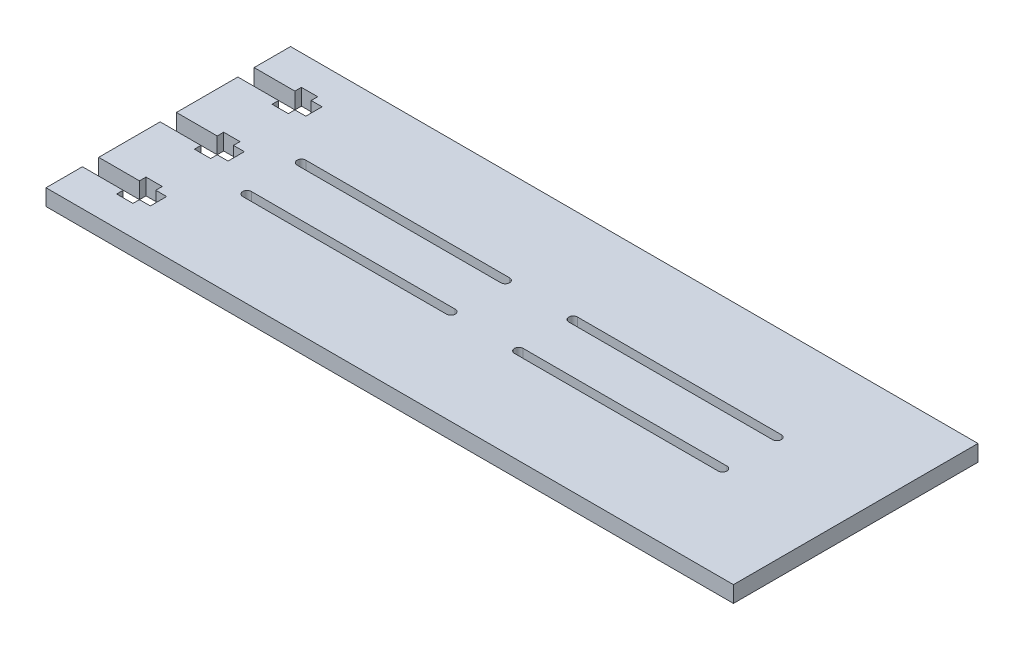
SolidWorks part; units mm, degrees
ref_plane "Front Plane" through (0, 0, 0) normal (0, 0, 1) x (1, 0, 0)
ref_plane "Top Plane" through (0, 0, 0) normal (0, 1, 0) x (1, 0, 0)
ref_plane "Right Plane" through (0, 0, 0) normal (1, 0, 0) x (0, 0, -1)
sketch "Sketch1" plane through (0, 0, 0) normal (0, 1, 0) x (1, 0, 0)
  line L1 (-126.5, -45) -> (126.5, -45)
  line L2 (-126.5, -45) -> (-126.5, 45)
  line L3 (-126.5, 45) -> (126.5, 45)
  line L4 (126.5, -45) -> (126.5, 45)
  line L5 (-126.5, -45) -> (126.5, 45) construction
  line L6 (-126.5, 45) -> (126.5, -45) construction
  point P0 (0, 0)
  dimension "D1" = 253
  dimension "D2" = 90
extrude "Boss-Extrude1" add sketch "Sketch1" along normal blind 6
sketch "Sketch2" plane through (0, 0, 0) normal (0, -1, 0) x (1, 0, 0)
  line L0 (87.5, 10) -> (12.5, 10) construction
  line L3 (87.5, 8.4) -> (12.5, 8.4)
  line L4 (87.5, 11.6) -> (12.5, 11.6)
  line L5 (126.5, 45) -> (126.5, -45) construction
  line L6 (-12.5, 10) -> (-87.5, 10) construction
  line L7 (-12.5, 8.4) -> (-87.5, 8.4)
  line L8 (-12.5, 11.6) -> (-87.5, 11.6)
  line L9 (87.5, -10) -> (12.5, -10) construction
  line L10 (87.5, -11.6) -> (12.5, -11.6)
  line L11 (87.5, -8.4) -> (12.5, -8.4)
  line L12 (-12.5, -10) -> (-87.5, -10) construction
  line L13 (-12.5, -11.6) -> (-87.5, -11.6)
  line L14 (-12.5, -8.4) -> (-87.5, -8.4)
  line L17 (-126.5, 45) -> (126.5, 45) construction
  arc A2 (87.5, 8.4) -> (87.5, 11.6) centre (87.5, 10) ccw
  arc A3 (12.5, 11.6) -> (12.5, 8.4) centre (12.5, 10) ccw
  arc A4 (-12.5, 8.4) -> (-12.5, 11.6) centre (-12.5, 10) ccw
  arc A5 (-87.5, 11.6) -> (-87.5, 8.4) centre (-87.5, 10) ccw
  arc A6 (87.5, -11.6) -> (87.5, -8.4) centre (87.5, -10) ccw
  arc A7 (12.5, -8.4) -> (12.5, -11.6) centre (12.5, -10) ccw
  arc A8 (-12.5, -11.6) -> (-12.5, -8.4) centre (-12.5, -10) ccw
  arc A9 (-87.5, -8.4) -> (-87.5, -11.6) centre (-87.5, -10) ccw
  point P3 (50, 10)
  point P14 (0, 0)
  point P17 (-50, 10)
  point P26 (50, -10)
  point P33 (-50, -10)
  point P39 (0, 0)
  dimension "D1" = 75
  dimension "D2" = 3.2
  dimension "D5" = 39
  dimension "D6" = 35
  dimension "D3" = 2
  dimension "D4" = 2
extrude "Cut-Extrude1" cut sketch "Sketch2" against normal through all
sketch "Sketch3" plane through (0, 6, 0) normal (0, 1, 0) x (1, 0, 0)
  line L0 (-126.5, 0) -> (-101.5, 0) construction
  line L1 (-126.5, 45) -> (-126.5, -45) construction
  line L2 (-126.5, 28.6) -> (-101.5, 28.6) construction
  line L3 (-126.5, -3) -> (-111.5, -3)
  line L4 (-126.5, 3) -> (-111.5, 3)
  line L5 (-126.5, -3) -> (-126.5, 3)
  line L6 (-101.5, -3) -> (-101.5, 3)
  line L7 (-126.5, 25.6) -> (-111.5, 25.6)
  line L8 (-126.5, 31.6) -> (-111.5, 31.6)
  line L9 (-126.5, 25.6) -> (-126.5, 31.6)
  line L10 (-101.5, 25.6) -> (-101.5, 31.6)
  line L11 (-105.5, 3) -> (-101.5, 3)
  line L12 (-111.5, -5.4) -> (-105.5, -5.4)
  line L13 (-111.5, -5.4) -> (-111.5, -3)
  line L14 (-111.5, 5.4) -> (-105.5, 5.4)
  line L15 (-105.5, -5.4) -> (-105.5, -3)
  line L16 (-111.5, -5.4) -> (-105.5, 5.4) construction
  line L17 (-111.5, 5.4) -> (-105.5, -5.4) construction
  line L18 (-111.5, 23.2) -> (-105.5, 23.2)
  line L19 (-111.5, 23.2) -> (-111.5, 25.6)
  line L20 (-111.5, 34) -> (-105.5, 34)
  line L21 (-105.5, 23.2) -> (-105.5, 25.6)
  line L22 (-111.5, 23.2) -> (-105.5, 34) construction
  line L23 (-111.5, 34) -> (-105.5, 23.2) construction
  line L24 (-126.5, 3) -> (-101.5, 3) construction
  line L25 (-105.5, -3) -> (-101.5, -3)
  line L26 (-126.5, -3) -> (-101.5, -3) construction
  line L27 (-105.5, 3) -> (-105.5, 5.4)
  line L28 (-111.5, 3) -> (-111.5, 5.4)
  line L29 (-105.5, 31.6) -> (-105.5, 34)
  line L30 (-105.5, 31.6) -> (-101.5, 31.6)
  line L31 (-126.5, 31.6) -> (-101.5, 31.6) construction
  line L32 (-105.5, 25.6) -> (-101.5, 25.6)
  line L33 (-126.5, 25.6) -> (-101.5, 25.6) construction
  line L34 (-111.5, 31.6) -> (-111.5, 34)
  line L35 (-111.5, -34) -> (-105.5, -23.2) construction
  line L36 (-111.5, -23.2) -> (-105.5, -34) construction
  line L37 (-126.5, -28.6) -> (-101.5, -28.6) construction
  line L38 (-111.5, -31.6) -> (-111.5, -34)
  line L39 (-105.5, -25.6) -> (-101.5, -25.6)
  line L40 (-105.5, -31.6) -> (-101.5, -31.6)
  line L41 (-105.5, -31.6) -> (-105.5, -34)
  line L42 (-105.5, -23.2) -> (-105.5, -25.6)
  line L43 (-111.5, -34) -> (-105.5, -34)
  line L44 (-111.5, -23.2) -> (-111.5, -25.6)
  line L45 (-111.5, -23.2) -> (-105.5, -23.2)
  line L46 (-101.5, -25.6) -> (-101.5, -31.6)
  line L47 (-126.5, -25.6) -> (-126.5, -31.6)
  line L48 (-126.5, -31.6) -> (-111.5, -31.6)
  line L49 (-126.5, -25.6) -> (-111.5, -25.6)
  point P11 (-108.5, 28.6)
  point P17 (-108.5, 0)
  point P47 (-108.5, -28.6)
  dimension "D3" = 25
  dimension "D4" = 28.6
  dimension "D7" = 15
  dimension "D8" = 10.8
  dimension "D9" = 6
  dimension "D1" = 3
  dimension "D2" = 3
  dimension "D5" = 3
  dimension "D6" = 3
extrude "Cut-Extrude2" cut sketch "Sketch3" against normal through all
